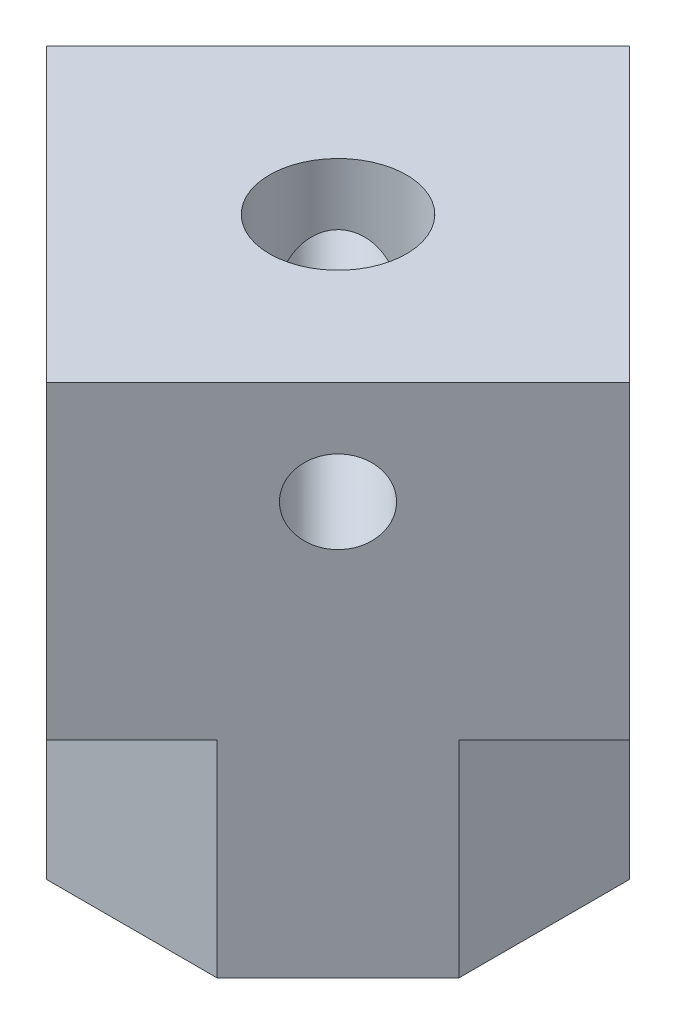
SolidWorks part; units mm, degrees
ref_plane "Front Plane" through (0, 0, 0) normal (0, 0, 1) x (1, 0, 0)
ref_plane "Top Plane" through (0, 0, 0) normal (0, 1, 0) x (1, 0, 0)
ref_plane "Right Plane" through (0, 0, 0) normal (1, 0, 0) x (0, 0, -1)
sketch "Sketch1" plane through (0, 0, 0) normal (0, 1, 0) x (1, 0, 0)
  line L0 (17.9605, 0) -> (0, 17.9605)
  line L3 (0, -17.9605) -> (17.9605, 0)
  line L6 (0, 17.9605) -> (-17.9605, 0)
  line L7 (-10.3695, 7.591) -> (-6.574, -6.574) [skipped]
  line L8 (-6.574, -6.574) -> (7.591, -10.3695) [skipped]
  line L9 (17.9605, 0) -> (14.165, 14.165) [skipped]
  line L10 (14.165, 14.165) -> (0, 17.9605) [skipped]
  line L11 (0, -17.9605) -> (-17.9605, 0)
  dimension "D1" = 25.4
extrude "Boss-Extrude1" add sketch "Sketch1" along normal blind 31.75
sketch "Sketch3" plane through (0, 0, 0) normal (0, -1, 0) x (1, 0, 0)
  line L0 (4.572, 0) -> (-4.572, 0) construction
  line L1 (4.572, 4.572) -> (-4.572, 4.572)
  line L2 (4.572, 4.572) -> (4.572, -4.572)
  line L3 (4.572, -4.572) -> (-4.572, -4.572)
  line L4 (-4.572, 4.572) -> (-4.572, -4.572)
  line L5 (4.572, 4.572) -> (-4.572, -4.572) construction
  line L6 (4.572, -4.572) -> (-4.572, 4.572) construction
  point P0 (0, 0)
  dimension "D1" = 9.144
extrude "Cut-Extrude2" cut sketch "Sketch3" against normal blind 12.7
hole_wizard "3/8-24 Tapped Hole1" positions "Sketch6" profile "Sketch7" tap size "3/8-24" standard "ANSI Inch"
sketch "Sketch6" plane through (0, 31.75, 0) normal (0, 1, 0) x (1, 0, 0)
  point P0 (0, 0)
cosmetic thread "Hole Thread1" parameters "D1"=19.05, "D2"=9.525
sketch "Sketch7" plane through (0, 31.75, 0) normal (1, 0, 0) x (0, 0, 1)
  line L0 (0, 0) -> (0, 17.7735)
  line L1 (0, 17.7735) -> (4.2164, 15.24)
  line L2 (4.2164, 15.24) -> (4.2164, 0)
  line L5 (4.2164, 0) -> (0, 0)
  line L10 (0, 17.7735) -> (-4.2164, 15.24) construction
  line L11 (0, -6.35) -> (0, 107.95) construction
  dimension "Tap Drill Dia." = 8.4328
  dimension "Tap Drill Depth" = 15.24
  dimension "Drill Angle" = 118
hole_wizard "1/4-20 Tapped Hole1" positions "Sketch8" profile "Sketch10" tap size "1/4-20" standard "ANSI Inch" end condition through all
sketch "Sketch8" plane through (-8.9803, 0, -8.9803) normal (-0.7071, 0, -0.7071) x (-0.7071, 0, 0.7071)
  line L0 (-12.7, 31.75) -> (12.7, 31.75) construction
  point P0 (0, 25.4)
  dimension "D1" = 6.35
sketch "Sketch10" plane through (-8.9803, 25.4, -8.9803) normal (0, 1, 0) x (-0.7071, 0, 0.7071)
  line L0 (0, 0) -> (0, 38.1)
  line L1 (0, 38.1) -> (2.5527, 38.1)
  line L2 (2.5527, 38.1) -> (2.5527, 0)
  line L5 (2.5527, 0) -> (0, 0)
  line L11 (0, -6.35) -> (0, 107.95) construction
  dimension "Thru Tap Drill Dia." = 5.1054
  dimension "Thru Tap Drill Depth" = 38.1
cosmetic thread "Hole Thread2" parameters "D2"=6.35
sketch "Sketch11" plane through (0, 0, 0) normal (0, -1, 0) x (1, 0, 0)
  line L0 (-12.7, -5.2605) -> (-12.7, 5.2605) construction
  line L1 (-12.7, 12.7) -> (12.7, 12.7)
  line L2 (-12.7, 12.7) -> (-12.7, -12.7)
  line L3 (-12.7, -12.7) -> (12.7, -12.7)
  line L4 (12.7, 12.7) -> (12.7, -12.7)
  line L5 (-12.7, 12.7) -> (12.7, -12.7) construction
  line L6 (-12.7, -12.7) -> (12.7, 12.7) construction
  line L7 (0, -17.9605) -> (-17.9605, 0) construction
  line L8 (-17.9605, 0) -> (0, 17.9605) construction
  line L9 (-5.2605, 12.7) -> (5.2605, 12.7) construction
  line L10 (0, 17.9605) -> (17.9605, 0) construction
  line L11 (-12.7, 5.2605) -> (-5.2605, 12.7) construction
  circle A0 centre (0, 0) radius 21.9137
  point P0 (0, 0)
extrude "Cut-Extrude3" cut sketch "Sketch11" against normal blind 12.7
hole_wizard "1/8 (0.125) Diameter Hole1" positions "Sketch12" profile "Sketch14" hole size "1/8" standard "ANSI Inch"
sketch "Sketch12" plane through (0, 0, 0) normal (0, -1, 0) x (-1, 0, 0)
  line L0 (4.572, -4.572) -> (-4.572, 4.572) construction
  line L1 (4.572, 4.572) -> (-4.572, -4.572) construction
  point P19 (4.572, -4.572)
  point P21 (-4.572, -4.572)
  point P23 (4.572, 4.572)
  point P25 (-4.572, 4.572)
sketch "Sketch14" plane through (-4.572, 0, 4.572) normal (1, 0, 0) x (0, 0, -1)
  line L0 (0, 0) -> (0, 13.6529)
  line L1 (0, 13.6529) -> (1.5875, 12.699)
  line L2 (1.5875, 12.699) -> (1.5875, 0)
  line L5 (1.5875, 0) -> (0, 0)
  line L10 (0, 13.6529) -> (-1.5875, 12.699) construction
  line L11 (0, -6.35) -> (0, 107.95) construction
  dimension "Hole Dia." = 3.175
  dimension "Hole Depth" = 12.699
  dimension "Drill Angle" = 118
hole_wizard "1/4-20 Tapped Hole2" positions "Sketch15" profile "Sketch16" tap size "1/4-20" standard "ANSI Inch"
sketch "Sketch15" plane through (-12.7, 0, 0) normal (-1, 0, 0) x (0, 0, 1)
  point P0 (0, 6.35)
  dimension "D1" = 6.35
sketch "Sketch16" plane through (-12.7, 6.35, 0) normal (0, 1, 0) x (0, 0, 1)
  line L0 (0, 0) -> (0, 17.271)
  line L1 (0, 17.271) -> (2.5527, 15.7372)
  line L2 (2.5527, 15.7372) -> (2.5527, 0)
  line L5 (2.5527, 0) -> (0, 0)
  line L10 (0, 17.271) -> (-2.5527, 15.7372) construction
  line L11 (0, -6.35) -> (0, 107.95) construction
  dimension "Tap Drill Dia." = 5.1054
  dimension "Tap Drill Depth" = 17.271
  dimension "Drill Angle" = 118
cosmetic thread "Hole Thread3" parameters "D1"=12.7, "D2"=6.35
